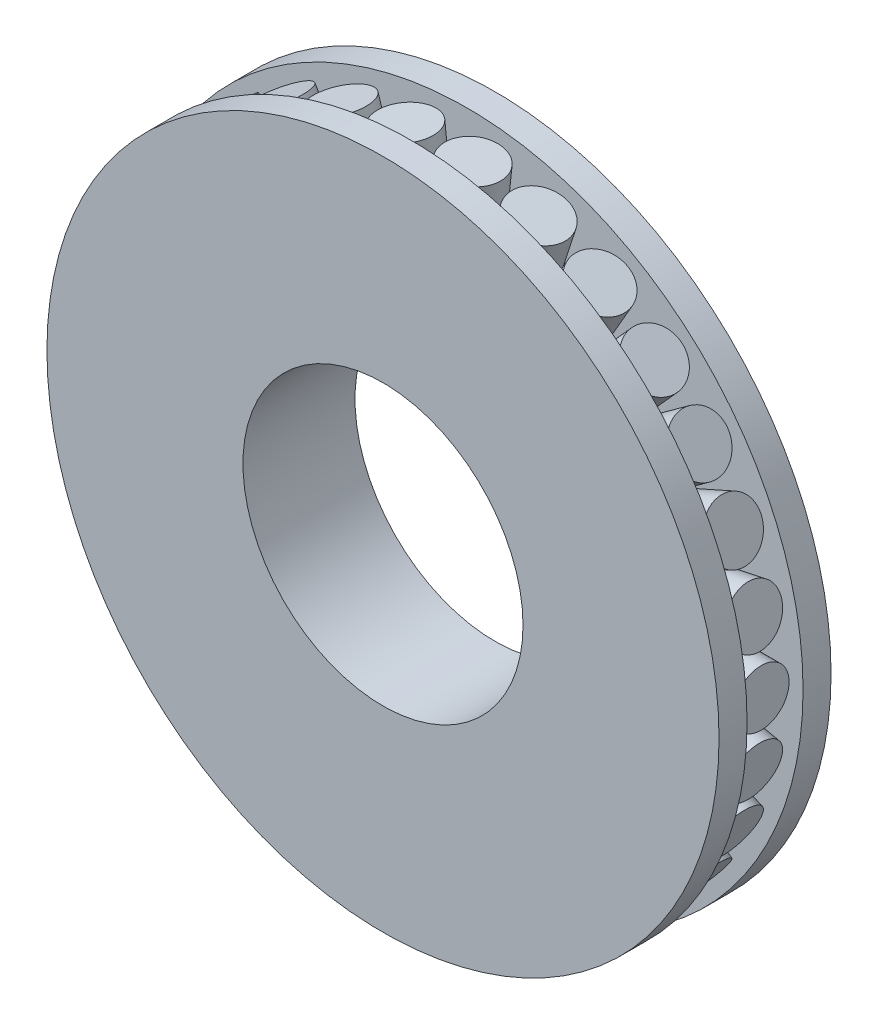
SolidWorks part; units mm, degrees
ref_plane "前视基准面" through (0, 0, 0) normal (0, 0, 1) x (1, 0, 0)
ref_plane "上视基准面" through (0, 0, 0) normal (0, 1, 0) x (1, 0, 0)
ref_plane "右视基准面" through (0, 0, 0) normal (1, 0, 0) x (0, 0, -1)
sketch "草图1" plane through (0, 0, 0) normal (0, 0, 1) x (1, 0, 0)
  circle A0 centre (0, 0) radius 5
  circle A1 centre (0, 0) radius 12
  dimension "D1" = 24
  dimension "D2" = 10
extrude "凸台-拉伸1" add sketch "草图1" along normal blind 4
ref_plane "基准面1" through (0, 0, 2) normal (0, 0, -1) x (-1, 0, 0)
sketch "草图2" plane through (0, 0, 2) normal (0, 0, -1) x (-1, 0, 0)
  circle A0 centre (0, 0) radius 7
  circle A1 centre (0, 0) radius 12
extrude "切除-拉伸1" cut sketch "草图2" along normal blind 1 and the other way blind 1
sketch "草图3" plane through (0, 0, 0) normal (0, 1, 0) x (1, 0, 0)
  line L0 (-6.9055, -2) -> (-17.9157, -2) construction
  line L1 (13.2, -2) -> (-13.2, -2) construction
ref_plane "基准面2" through (-11, 0, 0) normal (1, 0, 0) x (0, 0, -1)
sketch "草图4" plane through (-11, 0, 0) normal (1, 0, 0) x (0, 0, -1)
  line L0 (-2, -13.2) -> (-2, 13.2) construction
  circle A0 centre (-2, 0) radius 1
extrude "凸台-拉伸2" add sketch "草图4" along normal blind 4 and the other way blind 0.5 separate body
ref_axis "基准轴1" through (0, 0, 4) along (0, 0, -1)
pattern_circular "阵列(圆周)1" count 30 over 360 about axis through (0, 0, 4) along (0, 0, -1) of bodies 108
